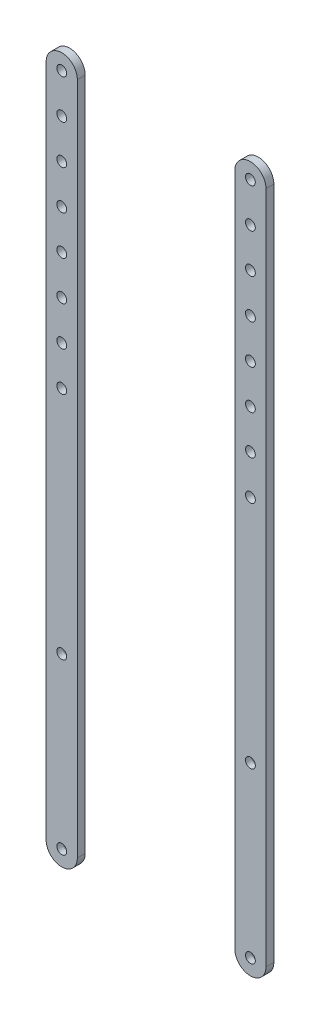
SolidWorks part; units mm, degrees
other "Markup1"
sketch "Sketch2" plane through (0.0463, -24.9703, 0) normal (0.1644, -0.1295, 0.9779) x (0.9753, 0.1699, -0.1414)
ref_plane "Front Plane" through (0, 0, 0) normal (0, 0, 1) x (1, 0, 0)
ref_plane "Top Plane" through (0, 0, 0) normal (0, 1, 0) x (1, 0, 0)
ref_plane "Right Plane" through (0, 0, 0) normal (1, 0, 0) x (0, 0, -1)
sketch "Skeleton" plane through (0, 0, 0) normal (0, 0, 1) x (1, 0, 0)
  line L12 (-10.421, 7.5043) -> (-18.2135, 7.5043)
  line L13 (0.0463, -8.9838) -> (0.0463, 9.017)
  line L14 (-129.9283, 9.017) -> (-129.9283, -8.983)
  line L15 (-111.6685, 7.5043) -> (-119.461, 7.5043)
  line L16 (-107.6558, 19.017) -> (-107.6558, 11.517)
  line L17 (-28.2135, 25.0043) -> (-101.6685, 25.0043)
  line L18 (-22.2262, 11.517) -> (-22.2262, 19.017)
  line L19 (-18.2135, -7.4703) -> (-10.421, -7.4703)
  line L20 (-22.2262, -18.983) -> (-22.2262, -11.483)
  line L21 (-101.6685, -24.9703) -> (-28.2135, -24.9703)
  line L22 (-107.6558, -11.483) -> (-107.6558, -18.983)
  line L23 (-119.461, -7.4703) -> (-111.6685, -7.4703)
  line L24 (-64.941, -24.9703) -> (-64.941, 25.0043) construction
  line L25 (-129.9283, 0.017) -> (0, 0) construction
  arc A24 (-22.2262, 11.517) -> (-18.2135, 7.5043) centre (-18.2135, 11.517) ccw
  arc A25 (-10.421, 7.5043) -> (-8.4147, 9.356) centre (-10.421, 9.517) ccw
  arc A26 (0.0463, 9.017) -> (-8.4147, 9.356) centre (-4.191, 9.0164) ccw
  arc A27 (-8.4147, -9.322) -> (0.0463, -8.9838) centre (-4.191, -8.9828) ccw
  arc A28 (-8.4147, -9.322) -> (-10.421, -7.4703) centre (-10.421, -9.483) ccw
  arc A29 (-119.461, -7.4703) -> (-121.4673, -9.322) centre (-119.461, -9.483) ccw
  arc A30 (-129.9283, -8.983) -> (-121.4673, -9.322) centre (-125.691, -8.9824) ccw
  arc A31 (-121.4673, 9.356) -> (-129.9283, 9.017) centre (-125.691, 9.0165) ccw
  arc A32 (-121.4673, 9.356) -> (-119.461, 7.5043) centre (-119.461, 9.517) ccw
  arc A33 (-111.6685, 7.5043) -> (-107.6558, 11.517) centre (-111.6685, 11.517) ccw
  arc A34 (-101.6685, 25.0043) -> (-107.6558, 19.017) centre (-101.6685, 19.017) ccw
  arc A35 (-22.2262, 19.017) -> (-28.2135, 25.0043) centre (-28.2135, 19.017) ccw
  arc A36 (-18.2135, -7.4703) -> (-22.2262, -11.483) centre (-18.2135, -11.483) ccw
  arc A37 (-28.2135, -24.9703) -> (-22.2262, -18.983) centre (-28.2135, -18.983) ccw
  arc A38 (-107.6558, -18.983) -> (-101.6685, -24.9703) centre (-101.6685, -18.983) ccw
  arc A39 (-107.6558, -11.483) -> (-111.6685, -7.4703) centre (-111.6685, -11.483) ccw
  arc A40 (-90.1911, -21.4831) -> (-87.6911, -21.4831) centre (-88.9411, -21.4831) ccw
  arc A41 (-87.6911, -21.4831) -> (-90.1911, -21.4831) centre (-88.9411, -21.4831) ccw
  arc A42 (-42.1911, -21.4831) -> (-39.6911, -21.4831) centre (-40.9411, -21.4831) ccw
  arc A43 (-39.6911, -21.4831) -> (-42.1911, -21.4831) centre (-40.9411, -21.4831) ccw
  arc A44 (-42.1911, 21.5169) -> (-39.6911, 21.5169) centre (-40.9411, 21.5169) ccw
  arc A45 (-39.6911, 21.5169) -> (-42.1911, 21.5169) centre (-40.9411, 21.5169) ccw
  arc A46 (-87.6911, 21.5169) -> (-90.1911, 21.5169) centre (-88.9411, 21.5169) ccw
  arc A47 (-90.1911, 21.5169) -> (-87.6911, 21.5169) centre (-88.9411, 21.5169) ccw
sketch "Sketch3" plane through (0, 0, 0) normal (0, 0, 1) x (1, 0, 0)
  line L0 (-88.9411, -21.4831) -> (-88.9411, 150.0117) construction
  line L1 (-92.9072, -21.4831) -> (-92.9072, 150.0117)
  line L2 (-84.9749, -21.4831) -> (-84.9749, 150.0117)
  line L3 (-64.941, -24.9703) -> (-64.941, 118.5169) construction
  line L4 (-40.9409, -21.4831) -> (-40.9409, 150.0117) construction
  line L5 (-36.9748, -21.4831) -> (-36.9748, 150.0117)
  line L6 (-44.9071, -21.4831) -> (-44.9071, 150.0117)
  line L7 (-129.9283, 0.017) -> (0, 0) construction
  line L8 (-129.9283, 0.017) -> (0, 0) construction
  arc A0 (-92.9072, -21.4831) -> (-84.9749, -21.4831) centre (-88.9411, -21.4831) ccw
  arc A1 (-84.9749, 150.0117) -> (-92.9072, 150.0117) centre (-88.9411, 150.0117) ccw
  arc A2 (-36.9748, -21.4831) -> (-44.9071, -21.4831) centre (-40.9409, -21.4831) cw
  arc A3 (-44.9071, 150.0117) -> (-36.9748, 150.0117) centre (-40.9409, 150.0117) cw
  arc A4 (-87.6911, -21.4831) -> (-90.1911, -21.4831) centre (-88.9411, -21.4831) ccw construction
  arc A5 (-90.1911, -21.4831) -> (-87.6911, -21.4831) centre (-88.9411, -21.4831) ccw construction
  arc A6 (-39.6911, -21.4831) -> (-42.1911, -21.4831) centre (-40.9411, -21.4831) ccw construction
  arc A7 (-42.1911, -21.4831) -> (-39.6911, -21.4831) centre (-40.9411, -21.4831) ccw construction
  arc A8 (-39.6911, 21.5169) -> (-42.1911, 21.5169) centre (-40.9411, 21.5169) ccw construction
  arc A9 (-42.1911, 21.5169) -> (-39.6911, 21.5169) centre (-40.9411, 21.5169) ccw construction
  arc A10 (-87.6911, 21.5169) -> (-90.1911, 21.5169) centre (-88.9411, 21.5169) ccw construction
  arc A11 (-90.1911, 21.5169) -> (-87.6911, 21.5169) centre (-88.9411, 21.5169) ccw construction
  arc A12 (-87.6911, -21.4831) -> (-90.1911, -21.4831) centre (-88.9411, -21.4831) ccw
  arc A13 (-90.1911, -21.4831) -> (-87.6911, -21.4831) centre (-88.9411, -21.4831) ccw
  arc A14 (-39.6911, -21.4831) -> (-42.1911, -21.4831) centre (-40.9411, -21.4831) ccw
  arc A15 (-42.1911, -21.4831) -> (-39.6911, -21.4831) centre (-40.9411, -21.4831) ccw
  arc A16 (-39.6911, 21.5169) -> (-42.1911, 21.5169) centre (-40.9411, 21.5169) ccw
  arc A17 (-42.1911, 21.5169) -> (-39.6911, 21.5169) centre (-40.9411, 21.5169) ccw
  arc A18 (-87.6911, 21.5169) -> (-90.1911, 21.5169) centre (-88.9411, 21.5169) ccw
  arc A19 (-90.1911, 21.5169) -> (-87.6911, 21.5169) centre (-88.9411, 21.5169) ccw
  arc A22 (-87.6911, 150.0117) -> (-90.1911, 150.0117) centre (-88.9411, 150.0117) ccw
  arc A23 (-90.1911, 150.0117) -> (-87.6911, 150.0117) centre (-88.9411, 150.0117) ccw
  arc A24 (-39.6909, 150.0117) -> (-42.191, 150.0117) centre (-40.9409, 150.0117) ccw
  arc A25 (-42.191, 150.0117) -> (-39.6909, 150.0117) centre (-40.9409, 150.0117) ccw
  circle A26 centre (-88.9411, 140.0117) radius 1.25
  circle A27 centre (-88.9411, 130.0117) radius 1.25
  circle A28 centre (-88.9411, 120.0117) radius 1.25
  circle A29 centre (-40.9409, 140.0117) radius 1.25
  circle A30 centre (-40.9409, 130.0117) radius 1.25
  circle A31 centre (-40.9409, 120.0117) radius 1.25
  circle A32 centre (-88.9411, 110.0117) radius 1.25
  circle A33 centre (-40.9409, 110.0117) radius 1.25
  circle A34 centre (-88.9411, 100.0117) radius 1.25
  circle A35 centre (-40.9409, 100.0117) radius 1.25
  circle A36 centre (-88.9411, 90.0117) radius 1.25
  circle A37 centre (-40.9409, 90.0117) radius 1.25
  circle A38 centre (-88.9411, 80.0117) radius 1.25
  circle A39 centre (-40.9409, 80.0117) radius 1.25
  point P3 (-88.9411, 64.2643)
  point P8 (-64.941, 25.0043)
  point P9 (-64.941, -24.9703)
  point P16 (-40.9409, 64.2643)
  dimension "D2" = 140
  dimension "D1" = 150
  dimension "D3" = 130
  dimension "D4" = 120
  dimension "D5" = 5
extrude "Boss-Extrude1" add sketch "Sketch3" along normal blind 2
fillet "Fillet1" radius 0.5 2 edges at (-39.6911, -21.4831, 0) (-39.6911, 21.5169, 0)
fillet "Fillet2" radius 0.5 2 edges at (-87.6911, -21.4831, 0) (-87.6911, 21.5169, 0)
